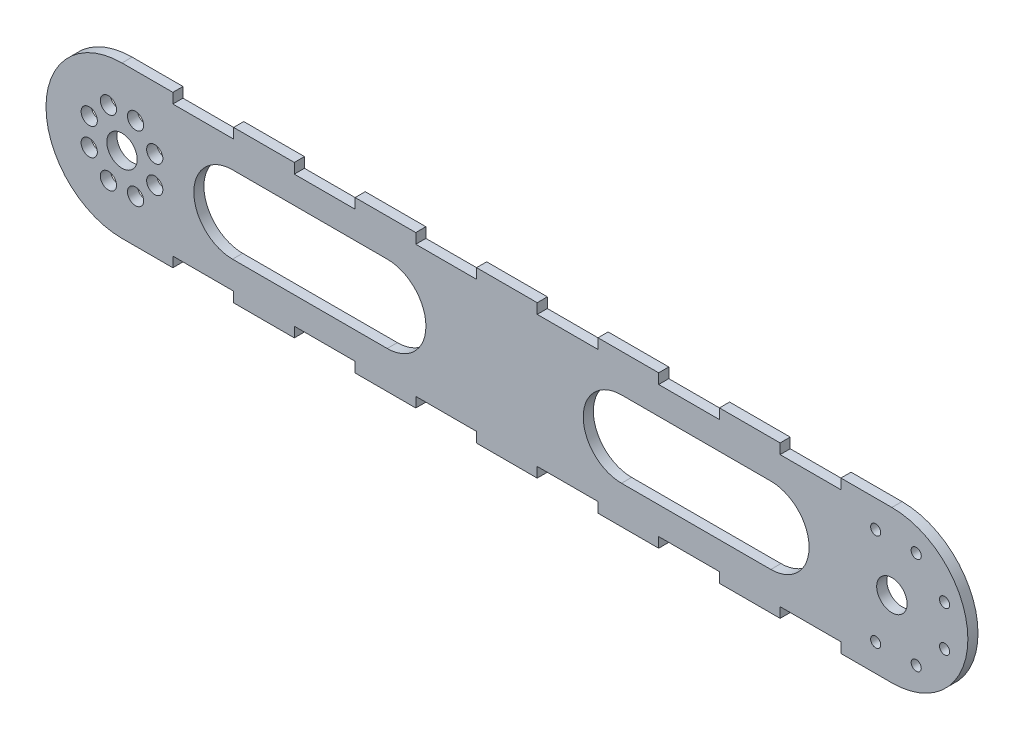
SolidWorks part; units mm, degrees
ref_plane "Front Plane" through (0, 0, 0) normal (0, 0, 1) x (1, 0, 0)
ref_plane "Top Plane" through (0, 0, 0) normal (0, 1, 0) x (1, 0, 0)
ref_plane "Right Plane" through (0, 0, 0) normal (1, 0, 0) x (0, 0, -1)
sketch "Sketch3" plane through (0, 0, 0) normal (0, 0, 1) x (1, 0, 0)
  line L0 (-20.9627, 0) -> (359.0373, 0) construction
  line L1 (-20.9627, 37.5) -> (359.0373, 37.5)
  line L2 (-20.9627, -37.5) -> (359.0373, -37.5)
  line L3 (33.6006, 0) -> (109.9507, 0) construction
  line L4 (33.6006, 19.0946) -> (109.9507, 19.0946)
  line L5 (33.6006, -19.0946) -> (109.9507, -19.0946)
  line L6 (225.5729, 0) -> (299.2902, 0) construction
  line L7 (225.5729, 18.8752) -> (299.2902, 18.8752)
  line L8 (225.5729, -18.8752) -> (299.2902, -18.8752)
  line L9 (-20.9627, 0) -> (-4.7949, 6.697)
  line L10 (-20.9627, 0) -> (-4.7949, 6.697) construction
  line L11 (-20.9627, 0) -> (-4.7949, -6.697) construction
  line L12 (64.0933, -37.5) -> (64.0933, -32.5)
  line L13 (124.0373, -37.5) -> (154.0373, -37.5)
  line L14 (124.0373, -37.5) -> (124.0373, -32.5)
  line L15 (124.0373, -32.5) -> (154.0373, -32.5)
  line L16 (154.0373, -37.5) -> (154.0373, -32.5)
  line L17 (64.0933, -37.5) -> (94.0933, -37.5)
  line L18 (94.0933, -37.5) -> (94.0933, -32.5)
  line L19 (64.0933, -32.5) -> (94.0933, -32.5)
  line L20 (4.1493, -37.5) -> (4.1493, -32.5)
  line L21 (4.1493, -37.5) -> (34.1493, -37.5)
  line L22 (34.1493, -37.5) -> (34.1493, -32.5)
  line L23 (4.1493, -32.5) -> (34.1493, -32.5)
  line L24 (183.9813, -37.5) -> (183.9813, -32.5)
  line L25 (183.9813, -37.5) -> (213.9813, -37.5)
  line L26 (213.9813, -37.5) -> (213.9813, -32.5)
  line L27 (183.9813, -32.5) -> (213.9813, -32.5)
  line L28 (243.9253, -37.5) -> (243.9253, -32.5)
  line L29 (243.9253, -37.5) -> (273.9253, -37.5)
  line L30 (273.9253, -37.5) -> (273.9253, -32.5)
  line L31 (243.9253, -32.5) -> (273.9253, -32.5)
  line L32 (303.8693, -37.5) -> (303.8693, -32.5)
  line L33 (303.8693, -37.5) -> (333.8693, -37.5)
  line L34 (333.8693, -37.5) -> (333.8693, -32.5)
  line L35 (303.8693, -32.5) -> (333.8693, -32.5)
  line L36 (-101.4371, 0) -> (436.7316, 0) construction
  line L37 (303.8693, 37.5) -> (333.8693, 37.5)
  line L38 (333.8693, 37.5) -> (333.8693, 32.5)
  line L39 (303.8693, 32.5) -> (333.8693, 32.5)
  line L40 (303.8693, 37.5) -> (303.8693, 32.5)
  line L41 (243.9253, 37.5) -> (273.9253, 37.5)
  line L42 (273.9253, 37.5) -> (273.9253, 32.5)
  line L43 (243.9253, 32.5) -> (273.9253, 32.5)
  line L44 (243.9253, 37.5) -> (243.9253, 32.5)
  line L45 (183.9813, 37.5) -> (213.9813, 37.5)
  line L46 (213.9813, 37.5) -> (213.9813, 32.5)
  line L47 (183.9813, 32.5) -> (213.9813, 32.5)
  line L48 (183.9813, 37.5) -> (183.9813, 32.5)
  line L49 (124.0373, 32.5) -> (154.0373, 32.5)
  line L50 (154.0373, 37.5) -> (154.0373, 32.5)
  line L51 (124.0373, 37.5) -> (154.0373, 37.5)
  line L52 (124.0373, 37.5) -> (124.0373, 32.5)
  line L53 (64.0933, 37.5) -> (94.0933, 37.5)
  line L54 (94.0933, 37.5) -> (94.0933, 32.5)
  line L55 (64.0933, 32.5) -> (94.0933, 32.5)
  line L56 (64.0933, 37.5) -> (64.0933, 32.5)
  line L57 (4.1493, 37.5) -> (34.1493, 37.5)
  line L58 (34.1493, 37.5) -> (34.1493, 32.5)
  line L59 (4.1493, 32.5) -> (34.1493, 32.5)
  line L60 (4.1493, 37.5) -> (4.1493, 32.5)
  arc A0 (-20.9627, 37.5) -> (-20.9627, -37.5) centre (-20.9627, 0) ccw
  arc A1 (359.0373, -37.5) -> (359.0373, 37.5) centre (359.0373, 0) ccw
  circle A2 centre (-20.9627, 0) radius 7.5
  circle A3 centre (359.0373, 0) radius 7.5
  arc A4 (33.6006, 19.0946) -> (33.6006, -19.0946) centre (33.6006, 0) ccw
  arc A5 (109.9507, -19.0946) -> (109.9507, 19.0946) centre (109.9507, 0) ccw
  arc A6 (225.5729, 18.8752) -> (225.5729, -18.8752) centre (225.5729, 0) ccw
  arc A7 (299.2902, -18.8752) -> (299.2902, 18.8752) centre (299.2902, 0) ccw
  circle A8 centre (-4.7949, 6.697) radius 4
  circle A9 centre (-4.7949, -6.697) radius 4
  circle A10 centre (-14.2658, -16.1679) radius 4
  circle A11 centre (-27.6597, -16.1679) radius 4
  circle A12 centre (-37.1306, -6.697) radius 4
  circle A13 centre (-37.1306, 6.697) radius 4
  circle A14 centre (-27.6597, 16.1679) radius 4
  circle A15 centre (-14.2658, 16.1679) radius 4
  circle A16 centre (385.0373, 10) radius 2.5
  circle A17 centre (371.0373, 24) radius 2.5
  circle A18 centre (351.0373, 24) radius 2.5
  circle A19 centre (385.0373, -10) radius 2.5
  circle A20 centre (371.0373, -24) radius 2.5
  circle A21 centre (351.0373, -24) radius 2.5
  point P3 (169.0373, 0)
  point P14 (71.7757, 0)
  point P19 (262.4316, 0)
  dimension "D2" = 37.5
  dimension "D3" = 15
  dimension "D4" = 15
  dimension "D7" = 8
  dimension "D21" = 5
  dimension "D22" = 5
  dimension "D23" = 5
  dimension "D1" = 380
  dimension "D5" = 17.5
  dimension "D6" = 22.5
  dimension "D9" = 45
  dimension "D10" = 5
  dimension "D11" = 30
  dimension "D12" = 15
  dimension "D15" = 24
  dimension "D16" = 24
  dimension "D17" = 8
  dimension "D18" = 20
  dimension "D19" = 26
  dimension "D20" = 10
  dimension "D13" = 3
  dimension "D14" = 4
  dimension "D8" = 8
extrude "Boss-Extrude1" add sketch "Sketch3" along normal blind 5 contours L2 A1 L1 L38 L39 L40 L42 L43 L44 L46 L47 L48 L50 L49 L52 L54 L55 L56 L58 L59 L60 A0 L20 L23 L22 L12 L19 L18 L14 L15 L16 L24 L27 L26 L28 L31 L30 L32 L35 region at (172.7827, 0, 0)
